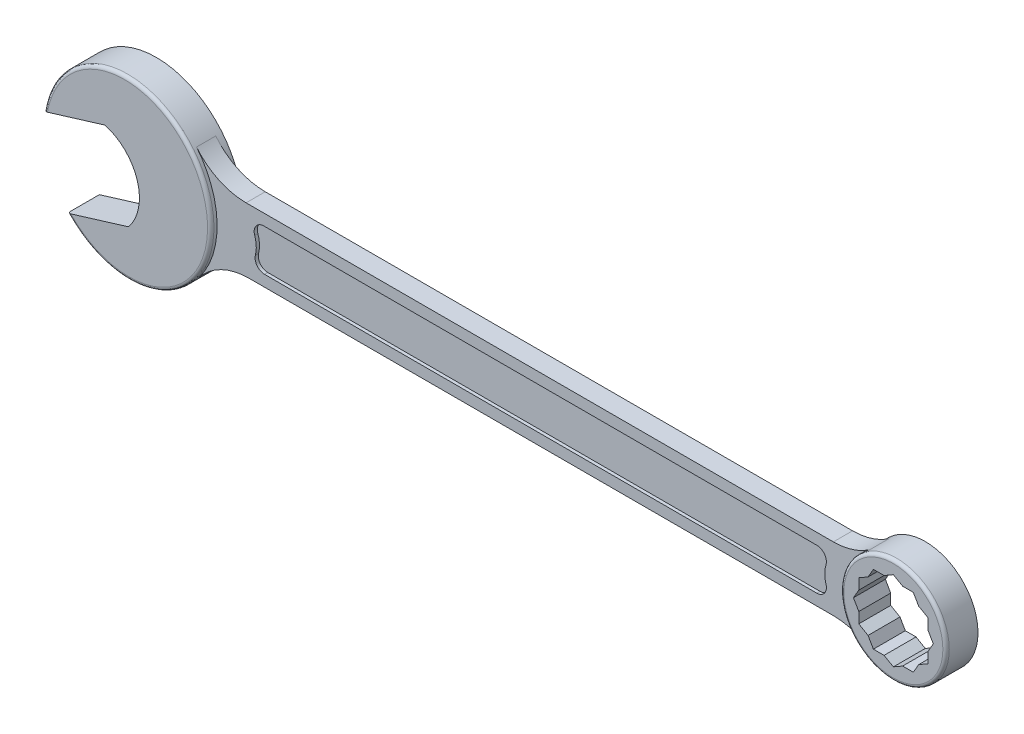
SolidWorks part; units mm, degrees
ref_plane "Front Plane" through (0, 0, 0) normal (0, 0, 1) x (1, 0, 0)
ref_plane "Top Plane" through (0, 0, 0) normal (0, 1, 0) x (1, 0, 0)
ref_plane "Right Plane" through (0, 0, 0) normal (1, 0, 0) x (0, 0, -1)
sketch "Sketch1" plane through (0, 0, 0) normal (0, 0, 1) x (1, 0, 0)
  line L0 (-63.1145, 0) -> (176.8855, 0) construction
  line L1 (-63.1145, 0) -> (-88.1145, -7.6433) construction
  line L2 (-71.1547, 26.2984) -> (-55.0743, -26.2984) construction
  line L3 (-69.9112, 10.9932) -> (-89.0372, 5.1458)
  line L4 (-62.6019, -12.9144) -> (-81.728, -18.7618)
  line L5 (173.9849, 10.8253) -> (170.6355, 10.8253)
  line L6 (176.8855, 12.5) -> (173.9849, 10.8253)
  line L7 (166.0602, 6.25) -> (166.0602, -6.25)
  line L8 (166.0602, -6.25) -> (168.9608, -7.9247)
  line L9 (176.8855, -12.5) -> (179.7861, -10.8253)
  line L10 (187.7108, -6.25) -> (187.7108, -2.9006)
  line L11 (187.7108, 6.25) -> (184.8102, 7.9247)
  line L12 (189.3855, 0) -> (187.7108, 2.9006)
  line L13 (183.1355, 10.8253) -> (179.7861, 10.8253)
  line L14 (170.6355, 10.8253) -> (168.9608, 7.9247)
  line L15 (164.3855, 0) -> (166.0602, -2.9006)
  line L16 (170.6355, -10.8253) -> (173.9849, -10.8253)
  line L17 (183.1355, -10.8253) -> (184.8102, -7.9247)
  line L18 (168.9608, 7.9247) -> (166.0602, 6.25)
  line L19 (166.0602, 2.9006) -> (164.3855, 0)
  line L20 (168.9608, -7.9247) -> (170.6355, -10.8253)
  line L21 (173.9849, -10.8253) -> (176.8855, -12.5)
  line L22 (179.7861, -10.8253) -> (183.1355, -10.8253)
  line L23 (184.8102, -7.9247) -> (187.7108, -6.25)
  line L24 (187.7108, -2.9006) -> (189.3855, 0)
  line L25 (187.7108, 2.9006) -> (187.7108, 6.25)
  line L26 (184.8102, 7.9247) -> (183.1355, 10.8253)
  line L27 (179.7861, 10.8253) -> (176.8855, 12.5)
  line L28 (-38.948, 10) -> (163.7611, 10)
  line L29 (-38.405, -10) -> (163.7611, -10)
  arc A0 (-69.9112, 10.9932) -> (-62.6019, -12.9144) centre (-74.1858, -3.3848) cw
  circle A1 centre (176.8855, 0) radius 16.5
  circle A2 centre (176.8855, 0) radius 10.8253 construction
  circle A3 centre (176.8855, 0) radius 10.8253 construction
  ellipse E0 centre (-63.1145, 0) end of major axis (-71.1547, 26.2984) minor radius 26.1423 (-81.728, -18.7618) -> (-89.0372, 5.1458) ccw
  point P44 (0, 0)
  point P46 (0, 0)
  point P47 (0, 0)
  dimension "D6" = 15
  dimension "D7" = 33
  dimension "D1" = 17
  dimension "D2" = 55
  dimension "D3" = 50
  dimension "D4" = 12.5
  dimension "D5" = 20
  dimension "D8" = 25
  dimension "D9" = 25
  dimension "D10" = 240
  dimension "D11" = 10
extrude "Boss-Extrude1" add sketch "Sketch1" along normal mid plane 10 contours L4 E0 L3 A0 | E0 L27 L13 L26 L11 L25 L12 L24 L10 L23 L17 L22 L9 L21 L16 L20 L8 L7 L15 L19 L18 L14 L5 L6 region at (-58.3814, 1.4417, 0) region at (182.0134, 15.1912, 0)
extrude "Boss-Extrude2" add sketch "Sketch1<4>" along normal mid plane 6 contours E0 L29 L28 region at (62.002, 0.0045, 0)
sketch "Sketch1<4>" plane through (0, 0, 0) normal (0, 0, 1) x (1, 0, 0) same geometry as "Sketch1"
fillet "Fillet1" radius 20 2 edges at (-38.405, -10, 0) (-38.948, 10, 0)
fillet "Fillet2" radius 20 2 edges at (163.7611, -10, 0) (163.7611, 10, 0)
sketch "Sketch4" plane through (0, 0, 3) normal (0, 0, 1) x (1, 0, 0)
  line L0 (156.0949, 6.5) -> (-27.7836, 6.5)
  line L1 (-26.832, -6.5) -> (156.0949, -6.5)
  line L2 (-26.832, -10) -> (156.0949, -10)
  line L3 (156.0949, 10) -> (-27.7836, 10)
  line L4 (-26.832, -10) -> (156.0949, -10)
  line L5 (156.0949, 10) -> (-27.7836, 10)
  arc A0 (-27.7836, 6.5) -> (-26.832, -6.5) centre (-33.8078, -0.4758) cw
  arc A1 (156.0949, 6.5) -> (156.0949, -6.5) centre (162.5949, 0) ccw
  arc A5 (-26.832, -10) -> (-42.5821, -17.6738) centre (-26.832, -30) ccw
  arc A6 (167.487, -13.5616) -> (156.0949, -10) centre (156.0949, -30) ccw
  arc A7 (167.487, 13.5616) -> (167.487, -13.5616) centre (176.8855, 0) ccw
  arc A8 (156.0949, 10) -> (167.487, 13.5616) centre (156.0949, 30) ccw
  arc A9 (-43.2953, 17.3752) -> (-27.7836, 10) centre (-27.7836, 30) ccw
  arc A10 (-26.832, -10) -> (-42.5821, -17.6738) centre (-26.832, -30) ccw
  arc A11 (167.487, -13.5616) -> (156.0949, -10) centre (156.0949, -30) ccw
  arc A12 (167.487, 13.5616) -> (167.487, -13.5616) centre (176.8855, 0) ccw
  arc A13 (156.0949, 10) -> (167.487, 13.5616) centre (156.0949, 30) ccw
  arc A14 (-43.2953, 17.3752) -> (-27.7836, 10) centre (-27.7836, 30) ccw
  ellipse E1 centre (-63.1145, 0) end of major axis (-71.1547, 26.2984) minor radius 26.1423 (-42.5821, -17.6738) -> (-43.2953, 17.3752) ccw
  ellipse E2 centre (-63.1145, 0) end of major axis (-71.1547, 26.2984) minor radius 26.1423 (-42.5821, -17.6738) -> (-43.2953, 17.3752) ccw
  dimension "D1" = 0
  dimension "D2" = 3.5
extrude "Cut-Extrude2" cut sketch "Sketch4" against normal blind 1 contours A1 L1 A0 L0
fillet "Fillet3" radius 3 4 edges at (156.0949, -6.5, 2.5) (156.0949, 6.5, 2.5) (-26.832, -6.5, 2.5) (-27.7836, 6.5, 2.5)
fillet "Fillet4" radius 1 2 edges at (193.3855, 0, 5) (-38.1145, 7.6433, 5)
sketch "Sketch5" plane through (0, 0, 2) normal (0, 0, 1) x (1, 0, 0)
  text T0 "2019 MC 253"
